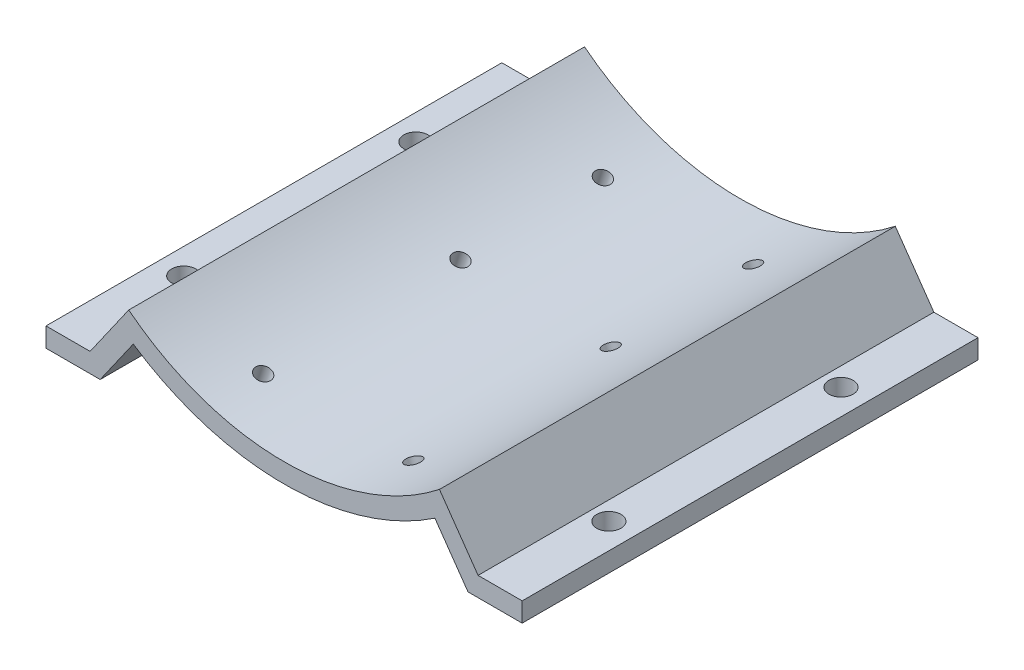
SolidWorks part; units mm, degrees
material "ASTM A36 Steel"
ref_plane "Front Plane" through (0, 0, 0) normal (0, 0, 1) x (1, 0, 0)
ref_plane "Top Plane" through (0, 0, 0) normal (0, 1, 0) x (1, 0, 0)
ref_plane "Right Plane" through (0, 0, 0) normal (1, 0, 0) x (0, 0, -1)
sketch "Sketch1" plane through (0, 0, 0) normal (0, 0, 1) x (1, 0, 0)
  line L0 (-60.3634, 0.6013) -> (-45.7945, 21.4077) construction
  line L1 (-78.1434, 6.9513) -> (-60.3634, 6.9513)
  line L2 (-78.1434, 6.9513) -> (-78.1434, 0.6013)
  line L3 (-78.1434, 0.6013) -> (-60.3634, 0.6013)
  line L4 (-60.3634, 6.9513) -> (-60.3634, 0.6013)
  line L5 (60.3634, 6.9513) -> (78.1434, 6.9513)
  line L6 (60.3634, 6.9513) -> (60.3634, 0.6013)
  line L7 (60.3634, 0.6013) -> (78.1434, 0.6013)
  line L8 (78.1434, 6.9513) -> (78.1434, 0.6013)
  line L9 (-60.3634, 0.6013) -> (-65.565, 4.2435)
  line L10 (-45.7945, 21.4077) -> (-50.9961, 25.0499)
  line L11 (-65.565, 4.2435) -> (-50.9961, 25.0499)
  line L12 (60.3634, 0.6013) -> (65.565, 4.2435)
  line L13 (60.3634, 0.6013) -> (45.7945, 21.4077) construction
  line L14 (65.565, 4.2435) -> (50.9961, 25.0499)
  line L15 (45.7945, 21.4077) -> (50.9961, 25.0499)
  line L16 (-49.4978, 16.1189) -> (-60.3634, 0.6013)
  line L17 (49.4978, 16.1189) -> (60.3634, 0.6013)
  circle A0 centre (0, 89.9645) radius 88.9 construction
  circle A1 centre (0, 89.9645) radius 82.55 construction
  arc A2 (-50.9961, 25.0499) -> (50.9961, 25.0499) centre (0, 89.9645) ccw
  arc A3 (49.4978, 16.1189) -> (-49.4978, 16.1189) centre (0, 89.9645) cw
  dimension "D13" = 165.1
  dimension "D14" = 177.8
  dimension "D1" = 17.78
  dimension "D2" = 6.35
  dimension "D3" = 6.35
  dimension "D4" = 17.78
  dimension "D7" = 125
  dimension "D8" = 6.35
  dimension "D9" = 125
  dimension "D10" = 6.35
  dimension "D11" = 25.4
  dimension "D12" = 25.4
extrude "Boss-Extrude1" add sketch "Sketch1" along normal blind 149.606 contours L14 L12 L7 L8 L5 | A3 L17 L6 L5 L14 A2 L11 L1 L4 L16 | L12 L14 L5 L6 | L9 L11 L1 L2 L3 | L11 L9 L4 L1 region at (-70.834, 3.6376, 0) region at (-56.2704, 15.2569, 0) region at (-62.3322, 4.3833, 0) region at (62.3322, 4.3833, 0) region at (70.834, 3.6376, 0)
sketch "Sketch2" plane through (0, 0, 149.606) normal (0, 0, 1) x (1, 0, 0)
  line L0 (-22.225, 10.4626) -> (22.225, 10.4626) construction
  line L1 (-27.073, 11.9802) -> (27.073, 11.9802) construction
  arc A0 (-50.9961, 25.0499) -> (50.9961, 25.0499) centre (0, 89.9645) ccw construction
  dimension "D1" = 44.45
  dimension "D2" = 5.08
sketch "Sketch3" plane through (0, 0, 0) normal (0, 0, -1) x (-1, 0, 0)
  line L0 (-27.073, 11.9802) -> (27.073, 11.9802) construction
  line L1 (-22.225, 10.4626) -> (22.225, 10.4626) construction
  arc A0 (-50.9961, 25.0499) -> (50.9961, 25.0499) centre (0, 89.9645) ccw construction
  dimension "D1" = 44.45
  dimension "D2" = 5.08
ref_axis "Axis1" through (27.073, 11.9802, 0) along (0, 0, 1)
ref_axis "Axis2" through (22.225, 10.4626, 149.606) along (0, 0, -1)
ref_axis "Axis3" through (-22.225, 10.4626, 149.606) along (0, 0, -1)
ref_axis "Axis4" through (-27.073, 11.9802, 149.606) along (0, 0, -1)
ref_plane "Plane1" through (-0.9994, 3.1926, 0) normal (0.2987, -0.9543, 0) x (-0.9543, -0.2987, 0)
ref_plane "Plane2" through (0.9994, 3.1926, 0) normal (0.2987, 0.9543, 0) x (0.9543, -0.2987, 0)
sketch "Sketch4" plane through (-0.9994, 3.1926, 0) normal (0.2987, -0.9543, 0) x (-0.9543, -0.2987, 0)
  line L0 (-24.3357, -149.606) -> (-24.3357, 0) construction
  line L1 (41.1841, 0) -> (-56.1508, 0) construction
  circle A0 centre (-26.8757, -131.826) radius 2.54
  circle A1 centre (-26.8757, -67.056) radius 2.54
  circle A2 centre (-26.8757, -20.32) radius 2.54
  dimension "D1" = 5.08
  dimension "D2" = 5.08
  dimension "D3" = 5.08
  dimension "D5" = 46.736
  dimension "D7" = 20.32
  dimension "D4" = 2.54
  dimension "D6" = 64.77
sketch "Sketch5" plane through (0.9994, 3.1926, 0) normal (0.2987, 0.9543, 0) x (0.9543, -0.2987, 0)
  line L0 (-24.3357, -149.606) -> (-24.3357, 0) construction
  line L1 (18.0846, 0) -> (-24.3357, 0) construction
  circle A0 centre (-26.8757, -20.32) radius 2.54
  circle A1 centre (-26.8757, -67.056) radius 2.54
  circle A2 centre (-26.8757, -131.826) radius 2.54
  dimension "D1" = 5.08
  dimension "D2" = 5.08
  dimension "D3" = 5.08
  dimension "D7" = 64.77
  dimension "D4" = 2.54
  dimension "D5" = 20.32
  dimension "D6" = 46.736
extrude "Cut-Extrude1" cut sketch "Sketch5" against normal blind 25.4 contours A0 | A1 | A2
extrude "Cut-Extrude2" cut sketch "Sketch4" along normal blind 25.4 contours A2 | A1 | A0
ref_plane "Plane3" through (0, 6.9513, 0) normal (0, 1, 0) x (1, 0, 0)
sketch "Sketch6" plane through (0, 6.9513, 0) normal (0, 1, 0) x (1, 0, 0)
  line L0 (-78.1434, -149.606) -> (-63.669, -149.606) construction
  line L1 (-78.1434, -149.606) -> (-78.1434, 0) construction
  line L2 (63.669, -149.606) -> (78.1434, -149.606) construction
  line L3 (78.1434, -149.606) -> (78.1434, 0) construction
  circle A0 centre (-69.7614, -36.576) radius 3.3655
  circle A1 centre (-69.7614, -112.776) radius 3.3655
  circle A2 centre (69.7614, -36.576) radius 3.3655
  circle A3 centre (69.7614, -112.776) radius 3.3655
  point P13 (70.9062, -149.606)
  dimension "D1" = 6.731
  dimension "D2" = 6.731
  dimension "D3" = 6.731
  dimension "D4" = 6.731
  dimension "D5" = 76.2
  dimension "D6" = 36.83
  dimension "D7" = 36.83
  dimension "D8" = 8.382
  dimension "D9" = 8.382
hole_wizard "Tap Drill for 3/8-16 Tap1" positions "Sketch8" profile "Sketch7" hole size "3/8-16" standard "ANSI Inch" end condition through all
sketch "Sketch8" plane through (0, 6.9513, 0) normal (0, 1, 0) x (1, 0, 0)
  point P0 (-69.7614, -112.776)
  point P3 (-69.7614, -36.576)
  point P6 (69.7614, -112.776)
  point P9 (69.7614, -36.576)
sketch "Sketch7" plane through (-69.7614, 6.9513, 112.776) normal (1, 0, 0) x (0, 0, 1)
  line L0 (0, 0) -> (0, 6.35)
  line L1 (0, 6.35) -> (3.9687, 6.35)
  line L2 (3.9687, 6.35) -> (3.9688, 0)
  line L5 (3.9688, 0) -> (0, 0)
  line L11 (0, -6.35) -> (0, 107.95) construction
  dimension "Thru Hole Dia." = 7.9375
  dimension "Thru Hole Depth" = 6.35
ref_axis "Axis5" through (-24.649, 11.2214, 131.826) along (0, 0, -1)
ref_axis "Axis6" through (24.649, 11.2214, 131.826) along (0, 0, -1)
equation "\"Var1\"=0.7"
equation "\"D1@Sketch1\"=\"Var1\""
equation "\"Var2\"=0.25"
equation "\"D2@Sketch1\"=\"Var2\""
equation "\"Var3\"=2.37651"
equation "\"D8@Sketch1\"=\"Var2\""
equation "\"Var4\"=1"
equation "\"D11@Sketch1\"=\"Var4\""
equation "\"Deg1\"=125"
equation "\"D7@Sketch1\"=\"Deg1\""
equation "\"D10@Sketch1\"=\"Var2\""
equation "\"D12@Sketch1\"=\"Var4\""
equation "\"D4@Sketch1\"=\"Var1\""
equation "\"D9@Sketch1\"=\"Deg1\""
equation "\"D3@Sketch1\"=\"Var2\""
equation "\"D13@Sketch1\"=6.5"
equation "\"Var8\"=0.2"
equation "\"D1@Sketch5\"=\"Var8\""
equation "\"D3@Sketch4\"=\"Var8\""
equation "\"D2@Sketch4\"=\"Var8\""
equation "\"D1@Sketch4\"=\"Var8\""
equation "\"D2@Sketch5\"=\"Var8\""
equation "\"D3@Sketch5\"=\"Var8\""
equation "\"D14@Sketch1\"=6.5+.5in"
